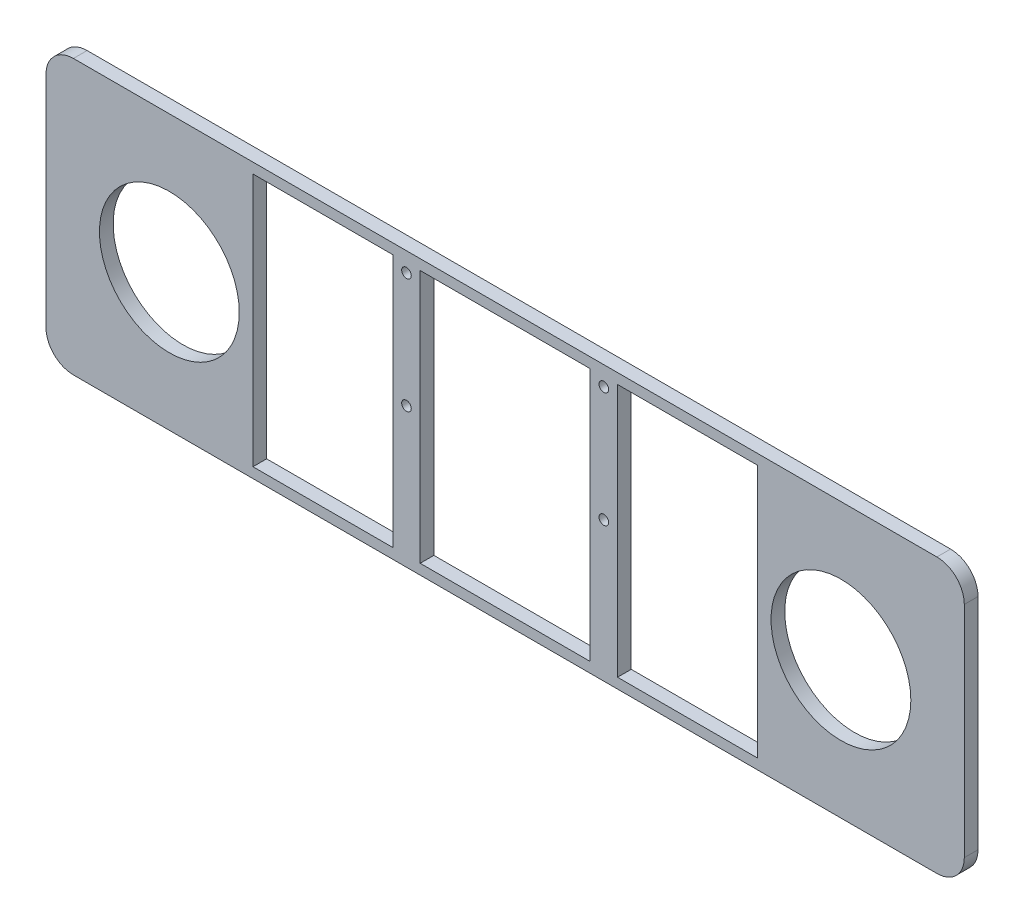
SolidWorks part; units mm, degrees
ref_plane "Front Plane" through (0, 0, 0) normal (0, 0, 1) x (1, 0, 0)
ref_plane "Top Plane" through (0, 0, 0) normal (0, 1, 0) x (1, 0, 0)
ref_plane "Right Plane" through (0, 0, 0) normal (1, 0, 0) x (0, 0, -1)
sketch "Sketch1" plane through (0, 0, 0) normal (0, 0, 1) x (1, 0, 0)
  line L0 (-31, 46.25) -> (31, 46.25)
  line L1 (-167.5, -50) -> (167.5, -50)
  line L2 (-167.5, -50) -> (-167.5, 50)
  line L3 (-167.5, 50) -> (167.5, 50)
  line L4 (167.5, -50) -> (167.5, 50)
  line L6 (-167.5, 50) -> (167.5, -50) construction
  line L11 (-41, -11.6692) -> (162.5, 46.25) construction
  line L12 (-41, 11.6692) -> (162.5, -46.25) construction
  line L16 (-31, -46.25) -> (-31, 46.25)
  line L22 (31, 46.25) -> (31, -46.25)
  line L25 (-31, -46.25) -> (31, -46.25)
  line L28 (0, 0) -> (-148, 0) construction
  line L29 (0, 0) -> (162.5, 0) construction
  line L30 (-41, -12.2388) -> (167.5, 50) construction
  line L31 (-41, 46.25) -> (-92, 46.25)
  line L32 (-41, 46.25) -> (-41, -46.25)
  line L33 (-41, -46.25) -> (-92, -46.25)
  line L34 (-92, 46.25) -> (-92, -46.25)
  line L35 (41, 46.25) -> (92, 46.25)
  line L36 (41, 46.25) -> (41, -46.25)
  line L37 (41, -46.25) -> (92, -46.25)
  line L38 (92, 46.25) -> (92, -46.25)
  circle A0 centre (-36, 43) radius 1.75
  circle A1 centre (36, 43) radius 1.75
  circle A2 centre (36, 1) radius 1.75
  circle A3 centre (-36, 1) radius 1.75
  circle A4 centre (-122.5, 0) radius 25.5
  circle A5 centre (122.5, 0) radius 25.5
  point P0 (0, 0)
  point P6 (0, 0)
  dimension "D9" = 36
  dimension "D13" = 51
  dimension "D1" = 335
  dimension "D2" = 100
  dimension "D3" = 10
  dimension "D4" = 92.5
  dimension "D5" = 51
  dimension "D6" = 10
  dimension "D7" = 62
  dimension "D8" = 31
  dimension "D12" = 43
  dimension "D10" = 2
  dimension "D11" = 2
extrude "Boss-Extrude1" add sketch "Sketch1" against normal blind 5
fillet "Fillet1" radius 10 4 edges at (167.5, -50, -2.5) (167.5, 50, -2.5) (-167.5, 50, -2.5) (-167.5, -50, -2.5)
